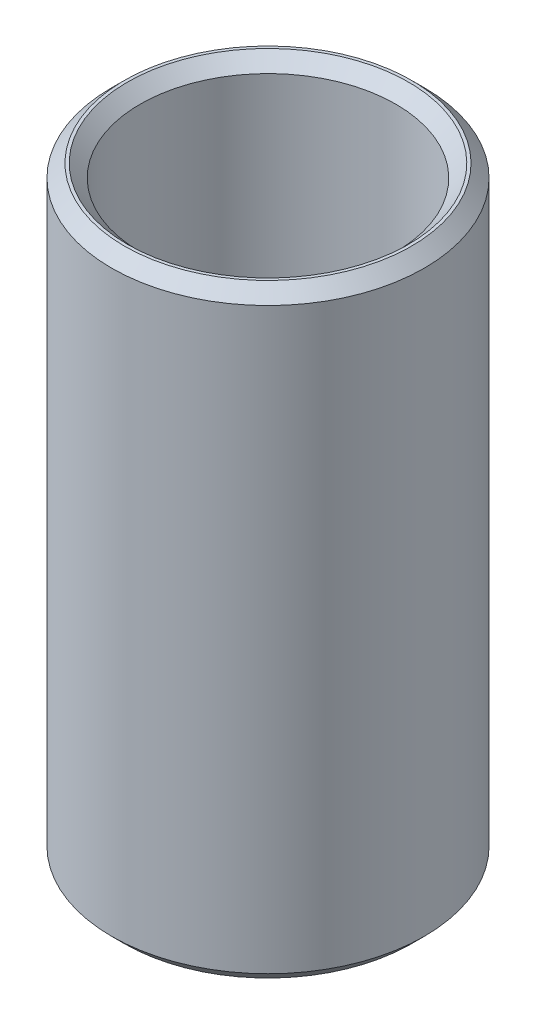
SolidWorks part; units mm, degrees
ref_plane "Front Plane" through (0, 0, 0) normal (0, 0, 1) x (1, 0, 0)
ref_plane "Top Plane" through (0, 0, 0) normal (0, 1, 0) x (1, 0, 0)
ref_plane "Right Plane" through (0, 0, 0) normal (1, 0, 0) x (0, 0, -1)
sketch "Sketch1" plane through (0, 0, 0) normal (0, 1, 0) x (1, 0, 0)
  circle A0 centre (0, 0) radius 37.5
  dimension "SLEEVE_OD" = 75
extrude "Boss-Extrude1" add sketch "Sketch1" along normal blind 144.9318
sketch "Sketch2" plane through (0, 0, 0) normal (0, 1, 0) x (1, 0, 0)
  circle A0 centre (0, 0) radius 30.6689
  dimension "BORE_D" = 61.3378
extrude "Cut-Extrude1" cut sketch "Sketch2" along normal through all
chamfer "Chamfer1" distance 3.0546 angle 45 4 edges at (0, 144.9318, 30.6689) (0, 0, 30.6689) (0, 0, 37.5) (0, 144.9318, 37.5)
